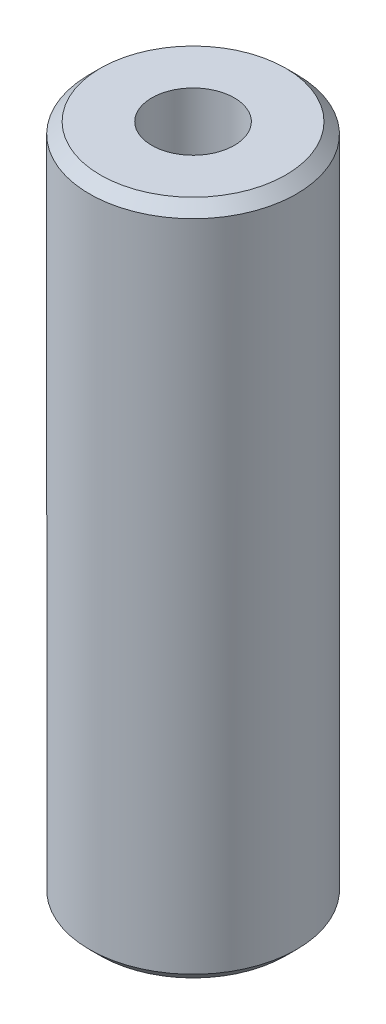
SolidWorks part; units mm, degrees
ref_plane "Front Plane" through (0, 0, 0) normal (0, 0, 1) x (1, 0, 0)
ref_plane "Top Plane" through (0, 0, 0) normal (0, 1, 0) x (1, 0, 0)
ref_plane "Right Plane" through (0, 0, 0) normal (1, 0, 0) x (0, 0, -1)
sketch "Sketch1" plane through (0, 0, 0) normal (0, 1, 0) x (1, 0, 0)
  circle A0 centre (0, 0) radius 12.5
  dimension "SHAFT_OD" = 25
extrude "Boss-Extrude1" add sketch "Sketch1" along normal blind 81.6412
sketch "Sketch2" plane through (0, 0, 0) normal (0, 1, 0) x (1, 0, 0)
  circle A0 centre (0, 0) radius 4.9812
  dimension "BORE_D" = 9.9623
extrude "Cut-Extrude1" cut sketch "Sketch2" along normal through all
chamfer "Chamfer1" distance 1.318 angle 45 2 edges at (0, 81.6412, 12.5) (0, 0, 12.5)
